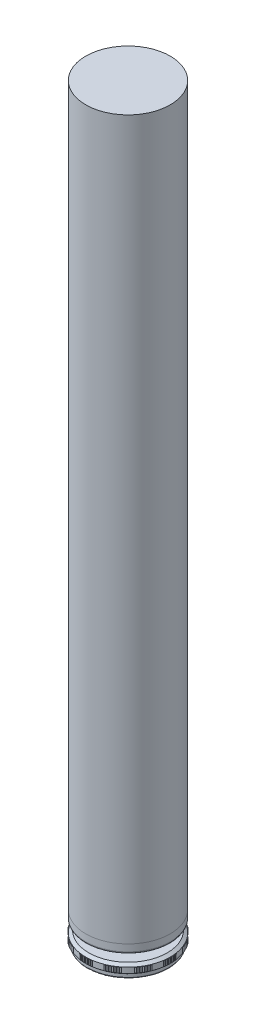
SolidWorks part; units mm, degrees
ref_plane "Plan de face" through (0, 0, 0) normal (0, 0, 1) x (1, 0, 0)
ref_plane "Plan de dessus" through (0, 0, 0) normal (0, 1, 0) x (1, 0, 0)
ref_plane "Plan de droite" through (0, 0, 0) normal (1, 0, 0) x (0, 0, -1)
sketch "Esquisse1" plane through (0, 0, 0) normal (0, 0, 1) x (1, 0, 0)
  line L0 (0, 36.3745) -> (0, -11.1903) construction
  line L1 (-25, 6.25) -> (-25, -2.25)
  line L2 (-25, 6.25) -> (-40, 6.25)
  line L3 (0, -14.75) -> (0, 14.75)
  line L4 (0, 14.75) -> (-40, 14.75)
  line L5 (-40, 6.25) -> (-40, 14.75)
  line L6 (-25, -2.25) -> (-40, -2.25)
  line L7 (-40, -2.25) -> (-40, -10.75)
  line L8 (-40, -10.75) -> (-38.5, -10.75)
  line L9 (-38.5, -10.75) -> (-38.5, -14.75)
  line L10 (-38.5, -14.75) -> (0, -14.75)
  dimension "D1" = 40
  dimension "D2" = 8.5
  dimension "D3" = 1.5
  dimension "D4" = 15
  dimension "D5" = 4
revolve "Révolution1" add sketch "Esquisse1" angle 360 about L0
chamfer "Chanfrein1" distance 2 angle 55 1 edges at (-40, -2.25, 0) first distance on face at (-40, -10.75, 0)
fillet "Congé1" radius 2 1 edges at (-40, 6.25, 0)
chamfer "Chanfrein2" distance 1.5 angle 40 1 edges at (-40, -10.75, 0) first distance on face at (-38.5, -10.75, 0)
fillet "Congé2" radius 1 1 edges at (-38.5, -14.75, 0)
ref_plane "Plan1" through (0, -4.25, 0) normal (0, -1, 0) x (1, 0, 0)
sketch "Esquisse2" plane through (0, -4.25, 0) normal (0, -1, 0) x (1, 0, 0)
  line L0 (0, -40) -> (0, 0) construction
  arc A0 (-6, -39.5474) -> (-4.9152, -39.6969) centre (-5.4581, -39.6259) ccw
  circle A1 centre (0, 0) radius 40 construction
  arc A2 (-4.9152, -39.6969) -> (-3.8268, -39.8165) centre (-4.3714, -39.7604) ccw
  arc A3 (-3.8268, -39.8165) -> (-2.7355, -39.9064) centre (-3.2814, -39.8652) ccw
  arc A4 (-2.7355, -39.9064) -> (-1.6421, -39.9663) centre (-2.189, -39.9401) ccw
  arc A5 (-1.6421, -39.9663) -> (-0.5475, -39.9963) centre (-1.0949, -39.985) ccw
  arc A6 (-0.5475, -39.9963) -> (0.5475, -39.9963) centre (0, -40) ccw
  arc A7 (0.5475, -39.9963) -> (1.6421, -39.9663) centre (1.0949, -39.985) ccw
  arc A8 (1.6421, -39.9663) -> (2.7355, -39.9064) centre (2.189, -39.9401) ccw
  arc A9 (2.7355, -39.9064) -> (3.8268, -39.8165) centre (3.2814, -39.8652) ccw
  arc A10 (3.8268, -39.8165) -> (4.9152, -39.6969) centre (4.3714, -39.7604) ccw
  arc A11 (4.9152, -39.6969) -> (6, -39.5474) centre (5.4581, -39.6259) ccw
  arc A12 (-6, -39.5474) -> (6, -39.5474) centre (0, 0) ccw
  dimension "D1" = 12
extrude "Boss.-Extru.1" add sketch "Esquisse2" along normal up to surface (5.2414 mm away) contours A12 A0 | A12 A2 | A12 A3 | A12 A4 | A12 A5 | A12 A6 | A12 A7 | A12 A8 | A12 A9 | A12 A10 | A12 A11 region at (-5.4897, -4.25, -39.8554) region at (5.4897, -4.25, -39.8554) region at (4.3967, -4.25, -39.9907) region at (3.3004, -4.25, -40.0961) region at (2.2017, -4.25, -40.1714) region at (1.1012, -4.25, -40.2166) region at (0, -4.25, -40.2317) region at (-1.1012, -4.25, -40.2166) region at (-2.2017, -4.25, -40.1714) region at (-3.3004, -4.25, -40.0961) region at (-4.3967, -4.25, -39.9907) up to face at (-38.5, -10.75, 0)
pattern_circular "Répétition circulaire1" count 12 over 360 about axis through (0, 36.3745, 0) along (0, 1, 0) of "Boss.-Extru.1"
sketch "Esquisse3" plane through (0, 14.75, 0) normal (0, 1, 0) x (1, 0, 0)
  circle A0 centre (0, 0) radius 40
  circle A1 centre (0, 0) radius 40 construction
extrude "Boss.-Extru.2" add sketch "Esquisse3" along normal blind 680 separate body
